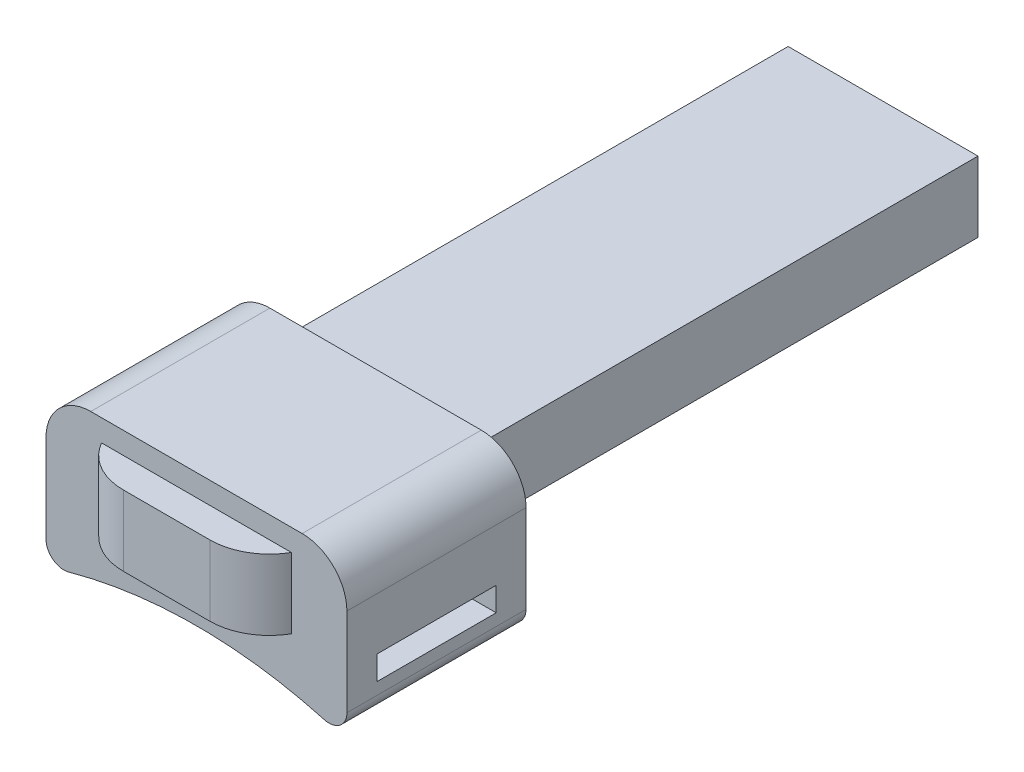
SolidWorks part; units mm, degrees
ref_plane "Front Plane" through (0, 0, 0) normal (0, 0, 1) x (1, 0, 0)
ref_plane "Top Plane" through (0, 0, 0) normal (0, 1, 0) x (1, 0, 0)
ref_plane "Right Plane" through (0, 0, 0) normal (1, 0, 0) x (0, 0, -1)
sketch "Sketch1" plane through (0, 0, 0) normal (0, 0, 1) x (1, 0, 0)
  line L0 (0, 0) -> (15.9, 0)
  line L1 (0, 0) -> (-15.9, 0)
  line L2 (-15.9, 0) -> (-15.9, 11.8)
  line L3 (-15.9, 11.8) -> (15.9, 11.8)
  line L4 (15.9, 11.8) -> (15.9, 0)
extrude "Boss-Extrude1" add sketch "Sketch1" against normal blind 120
ref_plane "Plane1" through (0, 0, -5) normal (0, 0, 1) x (1, 0, 0)
sketch "Sketch2" plane through (0, 0, -5) normal (0, 0, 1) x (1, 0, 0)
  line L3 (-15.9, 15.45) -> (17.7, 15.45)
  line L4 (25.2, 7.95) -> (25.2, -4.05)
  line L5 (-15.9, 15.45) -> (-17.7, 15.45)
  line L6 (-25.2, 7.95) -> (-25.2, -4.05)
  line L7 (-25.2, -4.05) -> (-25.2, -6.7991)
  line L9 (25.2, -6.7991) -> (25.2, -4.05)
  arc A0 (-17.7, 15.45) -> (-25.2, 7.95) centre (-17.7, 7.95) ccw
  arc A2 (21.3976, -9.6898) -> (25.2, -6.7991) centre (22.2, -6.7991) ccw
  arc A3 (-25.2, -6.7991) -> (-21.3976, -9.6898) centre (-22.2, -6.7991) ccw
  arc A4 (21.3976, -9.6898) -> (-21.3976, -9.6898) centre (0, -86.7751) ccw
  arc A5 (25.2, 7.95) -> (17.7, 15.45) centre (17.7, 7.95) ccw
  point P6 (0, 0)
  point P8 (0, 0)
  point P9 (0, 0)
  point P11 (0, -85.8939)
  point P14 (0, 0)
  point P16 (0, 0)
  point P18 (0, -90.0241)
  point P19 (0, -86.7751)
  dimension "D1" = 12
  dimension "D3" = 160
  dimension "D2" = 12
extrude "Boss-Extrude2" add sketch "Sketch2" against normal blind 30
fillet "Fillet1" radius 10 1 edges at (15.9, 5.9, 0)
fillet "Fillet2" radius 10 1 edges at (-15.9, 5.9, 0)
sketch "Sketch3" plane through (25.2, 0, 0) normal (1, 0, 0) x (0, 0, -1)
  line L2 (20, -4.7991) -> (30, -4.7991)
  line L3 (30, -4.7991) -> (30, -0.7991)
  line L4 (30, -0.7991) -> (10, -0.7991)
  line L5 (10, -0.7991) -> (10, -4.7991)
  line L6 (10, -4.7991) -> (20, -4.7991)
extrude "Cut-Extrude1" cut sketch "Sketch3" against normal blind 85
